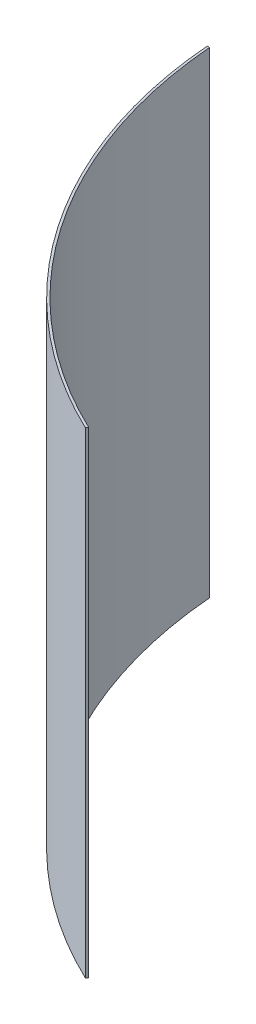
SolidWorks part; units mm, degrees
material "1060 Alloy"
ref_plane "Front Plane" through (0, 0, 0) normal (0, 0, 1) x (1, 0, 0)
ref_plane "Top Plane" through (0, 0, 0) normal (0, 1, 0) x (1, 0, 0)
ref_plane "Right Plane" through (0, 0, 0) normal (1, 0, 0) x (0, 0, -1)
sketch "Sketch1" plane through (0, 0, 0) normal (0, 1, 0) x (1, 0, 0)
  line L0 (-861.9527, -1815.8022) -> (-868.3277, -1823.844)
  line L1 (-2013.6591, -159.9282) -> (-2003.5072, -161.4282)
  arc A0 (-868.3277, -1823.844) -> (-2013.6591, -159.9282) centre (0, 0) cw
  arc A1 (-2003.5072, -161.4282) -> (-861.9527, -1815.8022) centre (0, 0) ccw
  point P6 (0, 0)
extrude "Boss-Extrude1" add sketch "Sketch1" along normal blind 2025.87
